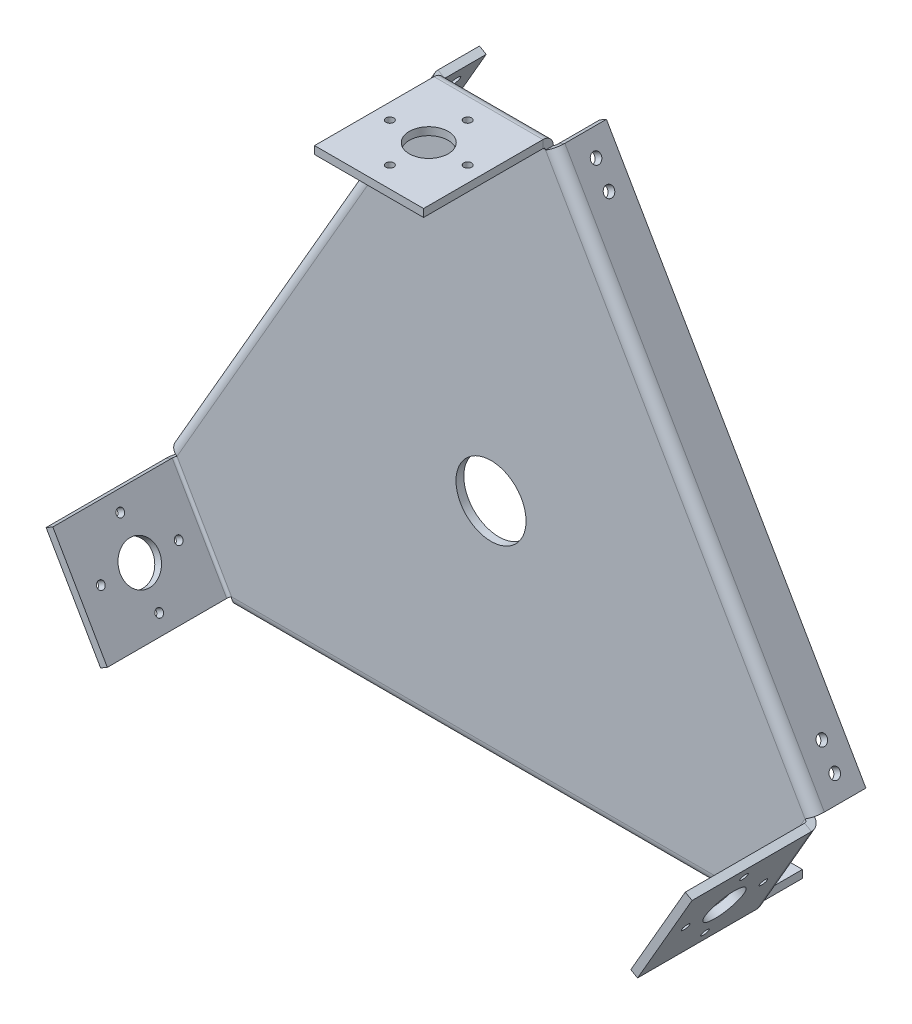
SolidWorks part; units mm, degrees
note: The reader was unsure of these and kept them because the rebuilt part matched: flange length of "Ребро-кромка2", "Ребро-кромка6".
ref_plane "Спереди" through (0, 0, 0) normal (0, 0, 1) x (1, 0, 0)
ref_plane "Сверху" through (0, 0, 0) normal (0, 1, 0) x (1, 0, 0)
ref_plane "Справа" through (0, 0, 0) normal (1, 0, 0) x (0, 0, -1)
sketch "Эскиз10" plane through (0, 0, 0) normal (0, 0, 1) x (1, 0, 0)
  line L0 (0, 0) -> (-21, 36.3731)
  line L1 (-21, 36.3731) -> (79, 209.5781)
  line L2 (79, 209.5781) -> (121, 209.5781)
  line L3 (121, 209.5781) -> (221, 36.3731)
  line L4 (221, 36.3731) -> (200, 0)
  line L5 (200, 0) -> (0, 0)
  dimension "D1" = 200
  dimension "D2" = 42
  dimension "D3" = 60
  dimension "D4" = 60
sheet metal parameters "Листовой металл3" thickness 3 parameters "D1"=0.7366
base flange "Базовая кромка3" sketch "Эскиз10" thickness 3 reverse thickness direction no parameters "D1"=0.7366
edge flange "Ребро-кромка2" sketch "Эскиз15" flange profiles "Эскиз15", "Эскиз30", "Эскиз32" flange angle 90 flange length 50 flange position bend outside bend radius 1 thickness 3 relief rectangular parameters "D6"=10, "D8"=1
sketch "Эскиз15" plane through (0, 209.5781, 0) normal (0, 1, 0) x (-1, 0, 0)
  line L2 (-121, 0) -> (-121, 47)
  line L3 (-121, 47) -> (-79, 47)
  line L4 (-79, 47) -> (-79, 0)
  line L7 (-121, 0) -> (-79, 0) construction
  line L8 (-121, 0) -> (-79, 0)
sketch "Эскиз30" plane through (0, 0, 0) normal (-0.866, -0.5, 0) x (0.5, -0.866, 0)
  line L0 (-42, 0) -> (0, 0) construction
  line L1 (-42, 0) -> (0, 0)
  line L2 (-42, 0) -> (-42, 47)
  line L3 (-42, 47) -> (0, 47)
  line L4 (0, 47) -> (0, 0)
sketch "Эскиз32" plane through (150, -86.6025, 0) normal (0.866, -0.5, 0) x (0.5, 0.866, 0)
  line L0 (100, 0) -> (142, 0) construction
  line L1 (100, 0) -> (142, 0)
  line L2 (100, 0) -> (100, 47)
  line L3 (100, 47) -> (142, 47)
  line L4 (142, 47) -> (142, 0)
bend "EdgeBend2" bend radius 1 bend angle 90 parameters "D5"=1
bend "EdgeBend8" bend radius 1 bend angle 90 parameters "D5"=7
bend "EdgeBend9" bend radius 1 bend angle 90 parameters "D5"=8
edge flange "Ребро-кромка6" sketch "Эскиз39" flange profiles "Эскиз39", "Эскиз40", "Эскиз41" flange angle 90 flange length 20 flange position bend outside bend radius 1 thickness 3 relief rectangular parameters "D6"=10, "D8"=1
sketch "Эскиз39" plane through (-31.5, 18.1865, -3) normal (-0.866, 0.5, 0) x (0.5, 0.866, 0)
  line L0 (221, 0) -> (21, 0) construction
  line L1 (221, 0) -> (21, 0)
  line L2 (21, 0) -> (21, 17)
  line L3 (21, 17) -> (221, 17)
  line L4 (221, 17) -> (221, 0)
sketch "Эскиз40" plane through (181.5, 104.7891, -3) normal (0.866, 0.5, 0) x (0.5, -0.866, 0)
  line L0 (79, 0) -> (-121, 0) construction
  line L1 (79, 0) -> (-121, 0)
  line L2 (-121, 0) -> (-121, 17)
  line L3 (-121, 17) -> (79, 17)
  line L4 (79, 17) -> (79, 0)
sketch "Эскиз41" plane through (0, 0, -3) normal (0, -1, 0) x (-1, 0, 0)
  line L0 (0, 0) -> (-200, 0) construction
  line L1 (0, 0) -> (-200, 0)
  line L2 (-200, 0) -> (-200, 17)
  line L3 (-200, 17) -> (0, 17)
  line L4 (0, 17) -> (0, 0)
bend "EdgeBend10" bend radius 1 bend angle 90 parameters "D5"=9
bend "EdgeBend11" bend radius 1 bend angle 90 parameters "D5"=10
bend "EdgeBend12" bend radius 1 bend angle 90 parameters "D5"=11
sketch "Эскиз42" plane through (0, 213.5781, 0) normal (0, 1, 0) x (1, 0, 0)
  line L0 (100, -1) -> (100, -47) construction
  line L1 (79, -1) -> (121, -1) construction
  line L2 (79, -47) -> (121, -47) construction
  line L3 (79, -24) -> (121, -24) construction
  line L4 (79, -1) -> (79, -47) construction
  line L5 (121, -47) -> (121, -1) construction
  circle A0 centre (100, -24) radius 7.5
  circle A1 centre (100, -9) radius 1.5
  circle A2 centre (115, -24) radius 1.5
  circle A3 centre (100, -39) radius 1.5
  circle A4 centre (85, -24) radius 1.5
  dimension "D1" = 15
  dimension "D3" = 3
  dimension "D4" = 15
  dimension "D2" = 15
extrude "Вырез-Вытянуть3" cut sketch "Эскиз42" against normal up to next normal cut yes
sketch "Эскиз43" plane through (153.4641, -88.6025, 0) normal (0.866, -0.5, 0) x (0, 0, -1)
  line L0 (-24, 142) -> (-24, 100) construction
  line L1 (-47, 121) -> (-1, 121) construction
  line L3 (-47, 100) -> (-1, 100) construction
  line L4 (-1, 142) -> (-47, 142) construction
  line L5 (-1, 142) -> (-1, 100) construction
  line L6 (-47, 142) -> (-47, 100) construction
  circle A0 centre (-24, 121) radius 7.5
  circle A1 centre (-24, 136) radius 1.5
  circle A2 centre (-9, 121) radius 1.5
  circle A3 centre (-24, 106) radius 1.5
  circle A4 centre (-39, 121) radius 1.5
  dimension "D1" = 15
  dimension "D2" = 3
  dimension "D3" = 15
  dimension "D4" = 15
extrude "Вырез-Вытянуть2" cut sketch "Эскиз43" against normal up to next normal cut yes
sketch "Эскиз44" plane through (-3.4641, -2, 0) normal (-0.866, -0.5, 0) x (0, 0, 1)
  line L0 (24, 42) -> (24, 0) construction
  line L1 (1, 21) -> (47, 21) construction
  line L2 (47, 42) -> (1, 42) construction
  line L3 (1, 0) -> (47, 0) construction
  line L4 (1, 0) -> (1, 42) construction
  line L5 (47, 0) -> (47, 42) construction
  circle A0 centre (24, 21) radius 7.5
  circle A1 centre (24, 36) radius 1.5
  circle A2 centre (39, 21) radius 1.5
  circle A3 centre (24, 6) radius 1.5
  circle A4 centre (9, 21) radius 1.5
  dimension "D1" = 3
  dimension "D2" = 15
  dimension "D3" = 15
  dimension "D4" = 15
extrude "Вырез-Вытянуть1" cut sketch "Эскиз44" against normal up to next normal cut yes
sketch "Эскиз47" plane through (-34.9641, 20.1865, 0) normal (-0.866, 0.5, 0) x (0, 0, 1)
  line L0 (-12, 21) -> (-12, 221) construction
  line L1 (-20, 21) -> (-4, 21) construction
  line L2 (-4, 221) -> (-20, 221) construction
  circle A0 centre (-12, 29) radius 2
  circle A1 centre (-12, 39) radius 2
  circle A2 centre (-12, 203) radius 2
  circle A3 centre (-12, 213) radius 2
  dimension "D1" = 4
  dimension "D4" = 4
  dimension "D2" = 10
  dimension "D3" = 8
  dimension "D5" = 10
  dimension "D6" = 8
extrude "Вырез-Вытянуть4" cut sketch "Эскиз47" against normal up to next normal cut yes
sketch "Эскиз50" plane through (184.9641, 106.7891, 0) normal (0.866, 0.5, 0) x (0, 0, -1)
  line L0 (12, -79) -> (12, 121) construction
  line L1 (4, -79) -> (20, -79) construction
  line L2 (20, 121) -> (4, 121) construction
  circle A0 centre (12, -71) radius 2
  circle A1 centre (12, -61) radius 2
  circle A2 centre (12, 103) radius 2
  circle A3 centre (12, 113) radius 2
  dimension "D3" = 4
  dimension "D1" = 8
  dimension "D2" = 10
  dimension "D4" = 8
  dimension "D5" = 10
extrude "Вырез-Вытянуть6" cut sketch "Эскиз50" against normal up to next normal cut yes
sketch "Эскиз51" plane through (0, -4, 0) normal (0, -1, 0) x (1, 0, 0)
  line L0 (200, -12) -> (0, -12) construction
  line L1 (200, -20) -> (200, -4) construction
  line L2 (0, -4) -> (0, -20) construction
  circle A0 centre (192, -12) radius 2
  circle A1 centre (182, -12) radius 2
  circle A2 centre (18, -12) radius 2
  circle A3 centre (8, -12) radius 2
  dimension "D3" = 4
  dimension "D1" = 10
  dimension "D2" = 8
  dimension "D4" = 10
  dimension "D5" = 8
extrude "Вырез-Вытянуть7" cut sketch "Эскиз51" against normal up to next normal cut yes
sketch "Эскиз52" plane through (0, 0, -3) normal (0, 0, -1) x (-1, 0, 0)
  line L0 (-100, 209.5781) -> (-100, -1) construction
  line L1 (-121, 209.5781) -> (-79, 209.5781) construction
  line L2 (0, -1) -> (-200, -1) construction
  line L3 (-210.5, 18.1865) -> (-29, 122.9756) construction
  line L5 (-79, 209.5781) -> (21, 36.3731) construction
  line L6 (-200, 0) -> (-221, 36.3731) construction
  circle A0 centre (-100, 81.9837) radius 13.5
  point P8 (0, 0)
  dimension "D1" = 27
extrude "Вырез-Вытянуть8" cut sketch "Эскиз52" against normal up to next normal cut yes
flat pattern "Развертка3" [suppressed]
sketch "Сгиб-Линии3" plane through (0, 0, 0) normal (0, 0, 1) x (1, 0, 0)
  line L0 (121, 211.2024) -> (79, 211.2024) construction
  line L1 (121, 211.2024) -> (79, 211.2024) construction
  line L2 (201.4066, -0.8121) -> (222.4066, 35.561) construction
  line L3 (-22.4066, 35.561) -> (-1.4066, -0.8121) construction
  line L4 (201.4066, -0.8121) -> (222.4066, 35.561) construction
  line L5 (-22.4066, 35.561) -> (-1.4066, -0.8121) construction
  line L6 (0, -1.6242) -> (200, -1.6242) construction
  line L7 (222.4066, 37.1852) -> (122.4066, 210.3902) construction
  line L8 (77.5934, 210.3902) -> (-22.4066, 37.1852) construction
  line L9 (0, -1.6242) -> (200, -1.6242) construction
  line L10 (222.4066, 37.1852) -> (122.4066, 210.3902) construction
  line L11 (77.5934, 210.3902) -> (-22.4066, 37.1852) construction
sketch3d "Граничная рамка3" [suppressed]
  line L0 (-63.6504, -24.6242, 0) -> (263.6504, -24.6242, 0) construction
  line L1 (-63.6504, 258.8266, 0) -> (263.6504, 258.8266, 0) construction
  line L2 (-63.6504, -24.6242, 0) -> (-63.6504, 258.8266, 0) construction
  line L3 (263.6504, -24.6242, 0) -> (263.6504, 258.8266, 0) construction
bend of the flat pattern "Плоское состояние-<EdgeBend2>1"
bend of the flat pattern "Плоское состояние-<EdgeBend8>1"
bend of the flat pattern "Плоское состояние-<EdgeBend9>1"
bend of the flat pattern "Плоское состояние-<EdgeBend10>1"
bend of the flat pattern "Плоское состояние-<EdgeBend11>1"
bend of the flat pattern "Плоское состояние-<EdgeBend12>1"
sketch "Эскиз42-1" [suppressed] plane through (0, 211.8266, -3) normal (0, 0, -1) x (1, 0, 0)
  line L0 (100, -1) -> (100, -47) construction
  line L3 (79, -24) -> (121, -24) construction
  circle A0 centre (100, -24) radius 7.5
  circle A1 centre (100, -9) radius 1.5
  circle A2 centre (115, -24) radius 1.5
  circle A3 centre (100, -39) radius 1.5
  circle A4 centre (85, -24) radius 1.5
  dimension "D1" = 15
  dimension "D3" = 3
  dimension "D4" = 15
  dimension "D2" = 15
sketch "Эскиз43-1" [suppressed] plane through (151.9472, -87.7267, -3) normal (0, 0, -1) x (-0.866, 0.5, 0)
  line L0 (-24, 142) -> (-24, 100) construction
  line L1 (-47, 121) -> (-1, 121) construction
  circle A0 centre (-24, 121) radius 7.5
  circle A1 centre (-24, 136) radius 1.5
  circle A2 centre (-9, 121) radius 1.5
  circle A3 centre (-24, 106) radius 1.5
  circle A4 centre (-39, 121) radius 1.5
  dimension "D1" = 15
  dimension "D2" = 3
  dimension "D3" = 15
  dimension "D4" = 15
